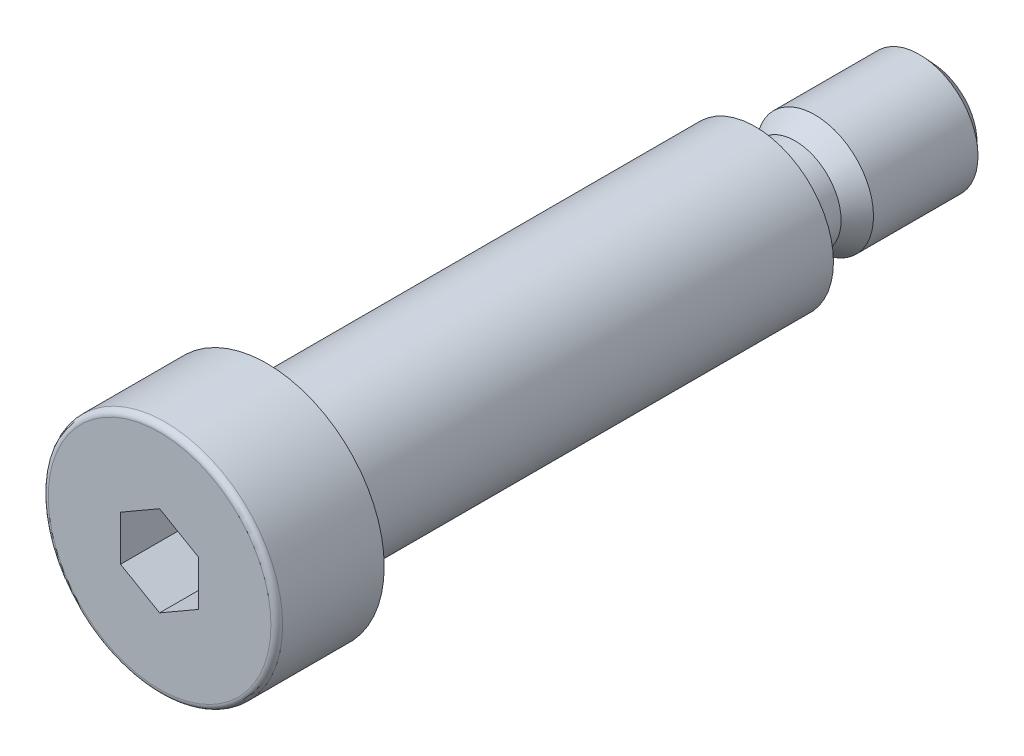
SolidWorks part; units mm, degrees
material "1.0545 (S355N)"
ref_plane "Płaszczyzna przednia" through (0, 0, 0) normal (0, 0, 1) x (1, 0, 0)
ref_plane "Płaszczyzna górna" through (0, 0, 0) normal (0, 1, 0) x (1, 0, 0)
ref_plane "Płaszczyzna prawa" through (0, 0, 0) normal (1, 0, 0) x (0, 0, -1)
sketch "Szkic1" plane through (0, 0, 0) normal (0, 1, 0) x (1, 0, 0)
  line L0 (6, 31.1) -> (4.7, 29.08)
  line L1 (12, -36) -> (-12, -36)
  line L2 (12, -36) -> (12, -25)
  line L3 (12, -25) -> (-12, -25)
  line L4 (-12, -36) -> (-12, -25)
  line L5 (8, -25) -> (-8, -25)
  line L6 (8, -25) -> (8, 25)
  line L7 (8, 25) -> (-8, 25)
  line L8 (-8, -25) -> (-8, 25)
  line L9 (-4.7, 25) -> (4.7, 25)
  line L10 (-4.7, 25) -> (-4.7, 29.08)
  line L11 (-4.7, 29.08) -> (4.7, 29.08)
  line L12 (4.7, 25) -> (4.7, 29.08)
  line L13 (6, 31.1) -> (6, 41.8)
  line L14 (6, 41.8) -> (4.7, 43)
  line L15 (4.7, 43) -> (-4.7, 43)
  line L16 (-4.7, 43) -> (-6, 41.8)
  line L17 (-6, 41.8) -> (-6, 31.1)
  line L18 (-6, 31.1) -> (-4.7, 29.08)
  line L19 (6, 31.1) -> (-6, 31.1) construction
  line L20 (6, 41.8) -> (-6, 41.8) construction
  line L21 (0, -19.9356) -> (0, 25.6583) construction
  line L22 (0, -36) -> (0, 43)
  point P4 (0, -25)
  point P14 (0, -25)
  point P15 (0, 25)
  point P16 (0, 25)
  point P17 (-8, 0)
  point P23 (0, 31.1)
  point P25 (0, 43)
  point P26 (0, 29.08)
  point P27 (0, 41.8)
  dimension "D1" = 24
  dimension "D2" = 11
  dimension "D3" = 16
  dimension "l1" = 50
  dimension "D5" = 9.4
  dimension "D6" = 18
  dimension "D7" = 12
  dimension "D8" = 9.4
  dimension "D9" = 1.2
  dimension "D10" = 2.02
  dimension "D11" = 10.7
revolve "Obrót1" add sketch "Szkic1" angle 360 about L22 region at (-2.35, 0, -27.04) region at (-2.934, 0, -36.0785) region at (-4, 0, 0) region at (-6, 0, 30.5)
sketch "Szkic2" plane through (0, 0, 36) normal (0, 0, 1) x (1, 0, 0)
  line L1 (4, 2.3094) -> (0, 4.6188)
  line L2 (0, 4.6188) -> (-4, 2.3094)
  line L3 (-4, 2.3094) -> (-4, -2.3094)
  line L4 (-4, -2.3094) -> (0, -4.6188)
  line L5 (0, -4.6188) -> (4, -2.3094)
  line L6 (4, -2.3094) -> (4, 2.3094)
  circle A0 centre (0, 0) radius 4 construction
  dimension "D1" = 8
extrude "Wytnij-wyciągnięcie1" cut sketch "Szkic2" against normal blind 6.6
fillet "Zaokrąglenie1" radius 0.6 1 edges at (12, 0, 36)
